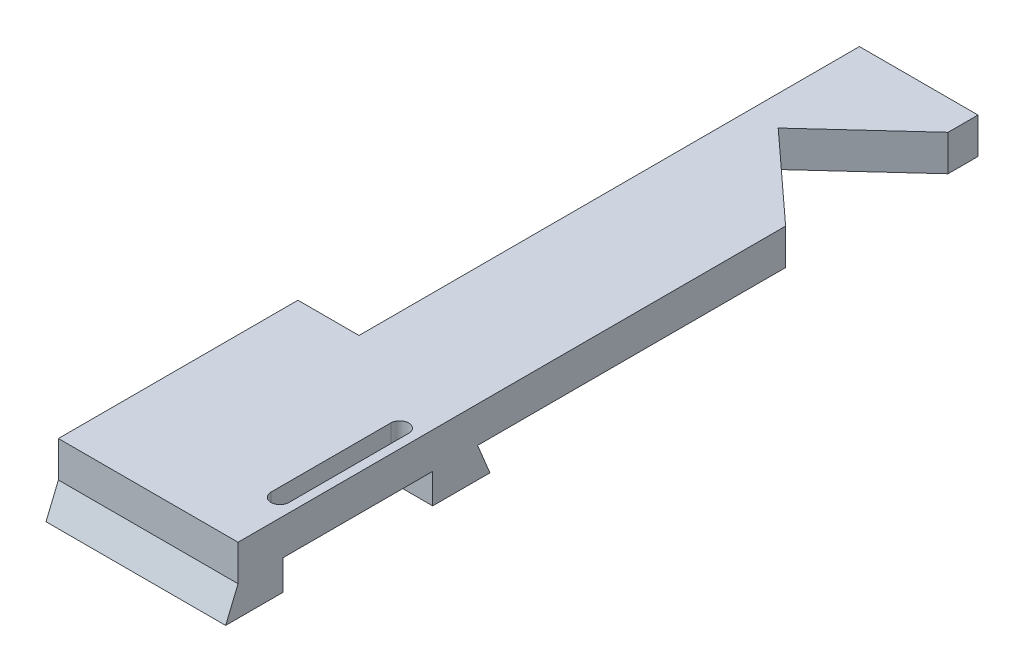
SolidWorks part; units mm, degrees
ref_plane "Front Plane" through (0, 0, 0) normal (0, 0, 1) x (1, 0, 0)
ref_plane "Top Plane" through (0, 0, 0) normal (0, 1, 0) x (1, 0, 0)
ref_plane "Right Plane" through (0, 0, 0) normal (1, 0, 0) x (0, 0, -1)
sketch "Sketch1" plane through (0, 0, 0) normal (0, 1, 0) x (1, 0, 0)
  line L0 (0, 8.1676) -> (-6.8534, 0)
  line L1 (-6.8534, 0) -> (0, -8.1676)
  line L2 (0, -8.1676) -> (0, -20)
  line L5 (0, 20) -> (0, 8.1676)
  line L6 (0, 0) -> (25.3033, 0) construction
  line L8 (-30, 20) -> (-30, -20)
  line L11 (-30, 20) -> (0, 20)
  line L12 (-30, -20) -> (0, -20)
  line L13 (0, -8.1676) -> (0, 8.1676)
  circle A0 centre (0, 0) radius 5.25 construction
  circle A1 centre (0, 0) radius 20 construction
  dimension "D2" = 10.5
  dimension "D7" = 40
  dimension "D1" = 100
  dimension "D4" = 30
extrude "Boss-Extrude1" add sketch "Sketch1" along normal blind 6 contours L8 L12 L2 L1 L0 L5 L11 | L1 L13 L0 region at (-2.2845, 0, 0) region at (-15.6222, 0, 0)
sketch "Sketch7" plane through (-30, 0, 0) normal (1, 0, 0) x (0, 0, -1)
  line L0 (20, -8.8983) -> (20, 12.3176) construction
  line L1 (-20, 13.2103) -> (-20, -9.9633) construction
  line L2 (0, 0) -> (0, -10.31) construction
  line L3 (-20, 0) -> (-21.8199, -5) construction
  line L4 (-21.8199, -5) -> (-12.5, -5)
  line L5 (-12.5, -5) -> (-12.5, 0)
  line L6 (-21.8199, -5) -> (-22.0699, -5)
  line L7 (-12.5, 0) -> (-20, 0)
  line L8 (12.5, 0) -> (20, 0)
  line L9 (12.5, -5) -> (12.5, 0)
  line L10 (21.8199, -5) -> (12.5, -5)
  line L11 (20, 0) -> (21.8199, -5) construction
  line L12 (20, 0) -> (-20, 0) construction
  line L13 (-22.0699, -5) -> (-20, 0)
  line L14 (22.0699, -5) -> (20, 0)
  line L15 (21.8199, -5) -> (22.0699, -5)
  point P15 (0, 0)
  dimension "D1" = 40
  dimension "D4" = 5
  dimension "D5" = 70
  dimension "D2" = 7.5
  dimension "D3" = 0.25
extrude "Boss-Extrude6" add sketch "Sketch7" along normal up to surface (30 mm away) contours L5 L4 L3 region at (-30, -2.601, 16.7884) up to face at (0, 3, 0)
extrude "Dove Boss" add sketch "Sketch7<3>" along normal up to surface (30 mm away) contours L11 L10 L9 region at (-30, -2.601, -16.7884) up to face at (0, 0.2857, 6.7243)
sketch "Sketch7<3>" plane through (-30, 0, 0) normal (1, 0, 0) x (0, 0, -1) same geometry as "Sketch7"
sketch "Sketch4" plane through (0, 0, 0) normal (0, 1, 0) x (1, 0, 0)
  line L0 (-3, 10) -> (-3, -10) construction
  line L1 (-1.5, 10) -> (-1.5, -10)
  line L2 (-4.5, 10) -> (-4.5, -10)
  arc A0 (-1.5, 10) -> (-4.5, 10) centre (-3, 10) ccw
  arc A1 (-4.5, -10) -> (-1.5, -10) centre (-3, -10) ccw
  point P2 (-3, 0)
  dimension "D1" = 3
  dimension "D2" = 3
  dimension "D4" = 20
extrude "Pin Slot" cut sketch "Sketch4" along normal up to next and the other way through all
sketch "Sketch8" plane through (0, 6, 0) normal (0, 1, 0) x (1, 0, 0)
  line L0 (0, 71.4366) -> (-14.8019, 85)
  line L1 (-19.8019, 103.5634) -> (0, 103.5634)
  line L2 (-19.8019, 103.5634) -> (-19.8019, 20)
  line L3 (-19.8019, 20) -> (0, 20)
  line L4 (0, 103.5634) -> (0, 98.5634)
  line L5 (-14.8019, 85) -> (0, 98.5634)
  line L6 (0, 71.4366) -> (0, 20)
  line L7 (20.6764, 85) -> (-23.1655, 85) construction
  line L8 (0, 71.4366) -> (0, 98.5634) construction
  line L11 (0, 20) -> (0, -20) construction
  circle A0 centre (0, 85) radius 10 construction
  point P18 (0, 0)
  dimension "D3" = 20
  dimension "D1" = 85
  dimension "D2" = 5
  dimension "D4" = 85
  dimension "D5" = 5
extrude "Boss-Extrude8" add sketch "Sketch8" against normal up to surface (6 mm away) up to face at (-3, 0, 0)
equation "\"doveAngle\"=70"
equation "\"D5@Sketch7\"=\"doveAngle\""
